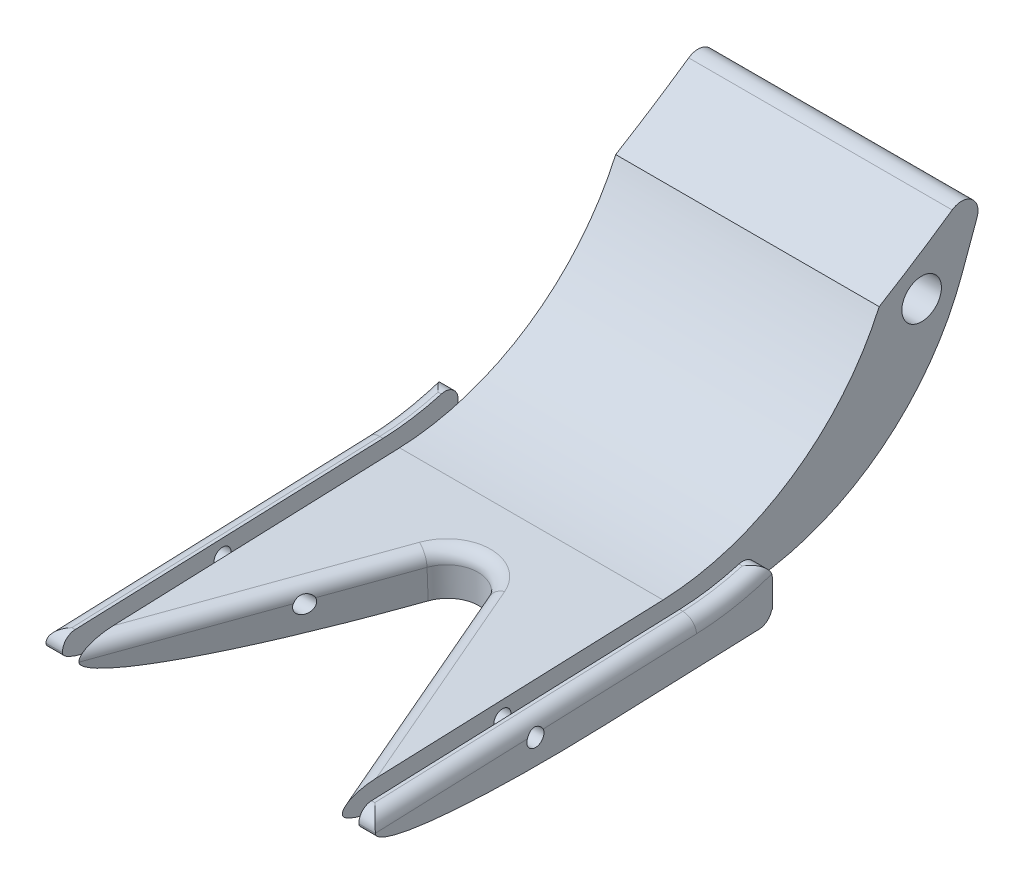
SolidWorks part; units mm, degrees
material "ABS"
ref_plane "Спереди" through (0, 0, 0) normal (0, 0, 1) x (1, 0, 0)
ref_plane "Сверху" through (0, 0, 0) normal (0, 1, 0) x (1, 0, 0)
ref_plane "Справа" through (0, 0, 0) normal (1, 0, 0) x (0, 0, -1)
sketch "Эскиз1" plane through (0, 0, 0) normal (1, 0, 0) x (0, 0, -1)
  line L0 (131.168, 18.7284) -> (135.7794, 31.3981)
  line L1 (40.4487, -21.4313) -> (-57.0595, -25.1154)
  line L2 (-62.2482, -20.119) -> (-62.2482, -15.3043)
  line L3 (-62.2482, -15.3043) -> (-136.0809, -38.1082)
  line L4 (-136.0809, -38.1082) -> (63.5227, -30.5666)
  circle A0 centre (118.9675, 18.4744) radius 6
  arc A1 (135.7794, 31.3981) -> (128.2349, 37.2192) centre (131.0809, 33.1082) ccw
  arc A2 (106.0731, 22.8759) -> (128.2349, 37.2192) centre (-113.2151, 385.9899) ccw
  arc A3 (40.4487, -21.4313) -> (106.0731, 22.8759) centre (37.617, 53.5152) ccw
  arc A4 (-62.2482, -20.119) -> (-57.0595, -25.1154) centre (-57.2482, -20.119) ccw
  arc A5 (63.5227, -30.5666) -> (131.168, 18.7284) centre (60.691, 44.3799) ccw
extrude "Бобышка-Вытянуть1" add sketch "Эскиз1" along normal blind 80
sketch "Эскиз3" plane through (0, -22.9268, -0.8662) normal (0, 0.9993, 0.0378) x (1, 0, 0)
  line L0 (0, -57.967) -> (40, 39.6107)
  line L1 (80, 39.6107) -> (0, 39.6107) construction
  line L2 (40, 39.6107) -> (80, -57.967)
  line L3 (80, -57.967) -> (80, -145.8098)
  line L4 (80, -145.8098) -> (0, -145.8098)
  line L5 (0, -145.8098) -> (0, -57.967)
extrude "Вырез-Вытянуть1" cut sketch "Эскиз3" against normal through all both and the other way through all
fillet "Скругление1" radius 10 1 edges at (40, -26.4277, -40.6375)
sketch "Эскиз4" plane through (0, 0, 0) normal (-1, 0, 0) x (0, 0, 1)
  circle A0 centre (8.3054, -28.2769) radius 2.6
extrude "Вырез-Вытянуть2" cut sketch "Эскиз4" against normal through all
sketch "Эскиз5" plane through (0, -32.9197, -1.2438) normal (0, -0.9993, -0.0378) x (1, 0, 0)
  line L1 (0, 57.967) -> (0, -62.3233) construction
  line L4 (30.7473, -17.0392) -> (0, 57.967) construction
  line L10 (80, -62.3233) -> (90, -62.3233)
  line L12 (90, 57.967) -> (80, 57.967)
  line L13 (0, 57.967) -> (-10, 57.967)
  line L15 (80, 57.967) -> (49.2527, -17.0392)
  line L16 (30.7473, -17.0392) -> (0, 57.967)
  line L17 (0, 57.967) -> (0, -62.3233)
  line L18 (0, -62.3233) -> (80, -62.3233)
  line L19 (80, -62.3233) -> (80, 57.967)
  line L20 (80, 57.967) -> (49.2527, -17.0392)
  line L21 (30.7473, -17.0392) -> (0, 57.967)
  line L23 (0, -62.3233) -> (80, -62.3233)
  line L25 (-10, -62.3233) -> (0, -62.3233)
  line L26 (-10, 57.967) -> (-10, -62.3233)
  line L32 (90, -62.3233) -> (90, 57.967)
  arc A2 (30.7473, -17.0392) -> (49.2527, -17.0392) centre (40, -13.2462) ccw
  arc A3 (30.7473, -17.0392) -> (49.2527, -17.0392) centre (40, -13.2462) ccw
  dimension "D1" = 0
extrude "Бобышка-Вытянуть2" add sketch "Эскиз5" along normal blind 3
sketch "Эскиз6" plane through (-10, 0, 0) normal (-1, 0, 0) x (0, 0, 1)
  line L10 (-63.636, -33.5645) -> (-63.0122, -17.0545)
  line L11 (56.5686, -38.1062) -> (-63.636, -33.5645) construction
  line L12 (56.5686, -38.1062) -> (57.0595, -25.1154)
  line L14 (-63.636, -33.5645) -> (56.5686, -38.1062)
  line L19 (57.0595, -25.1154) -> (-40.4487, -21.4313)
  circle A10 centre (8.3054, -28.2769) radius 2.6
  arc A19 (-63.0122, -17.0545) -> (-40.4487, -21.4313) centre (-37.617, 53.5152) ccw
extrude "Бобышка-Вытянуть3" add sketch "Эскиз6" against normal blind 5
sketch "Эскиз7" plane through (90, 0, 0) normal (1, 0, 0) x (0, 0, -1)
  line L10 (-56.5686, -38.1062) -> (-57.0595, -25.1154)
  line L11 (63.636, -33.5645) -> (-56.5686, -38.1062) construction
  line L13 (63.636, -33.5645) -> (63.636, -16.8269)
  line L14 (63.636, -33.5645) -> (63.5227, -30.5666) construction
  line L15 (-56.5686, -38.1062) -> (63.636, -33.5645)
  line L16 (40.4487, -21.4313) -> (-57.0595, -25.1154)
  circle A10 centre (-8.3054, -28.2769) radius 2.6
  arc A17 (40.4487, -21.4313) -> (63.636, -16.8269) centre (37.617, 53.5152) ccw
  arc A19 (63.5227, -30.5666) -> (63.636, -30.5623) centre (60.691, 44.3799) ccw
  line M12 (63.5227, -30.5666) -> (-56.6819, -35.1083)
extrude "Бобышка-Вытянуть4" add sketch "Эскиз7" against normal blind 5 contours A19 L13 A17 L16 L10 A10 M12 region at (90, -27.6334, -4.8646)
fillet "Скругление2" radius 4 12 edges at (-10, -20.1124, -51.8991) (90, -20.0484, -52.2249) (15.3736, -23.6995, 19.5831) (40, -22.0492, -24.0959) (-10, -23.2734, 8.3054) (90, -23.2734, 8.3054) (64.6264, -23.6995, 19.5831) (-7.5, -25.1154, 57.0595) (-7.5, -17.0545, -63.0122) (87.5, -16.8269, -63.636) (40, -33.5645, -63.636) (87.5, -25.1154, 57.0595)
fillet "Скругление3" radius 9 1 edges at (-5, -38.1062, 56.5686) second distance 70 first distance on face at (-5, -34.109, 56.7197)
fillet "Скругление4" radius 9 1 edges at (85, -38.1062, 56.5686) second distance 70 first distance on face at (85, -34.109, 56.7197)
